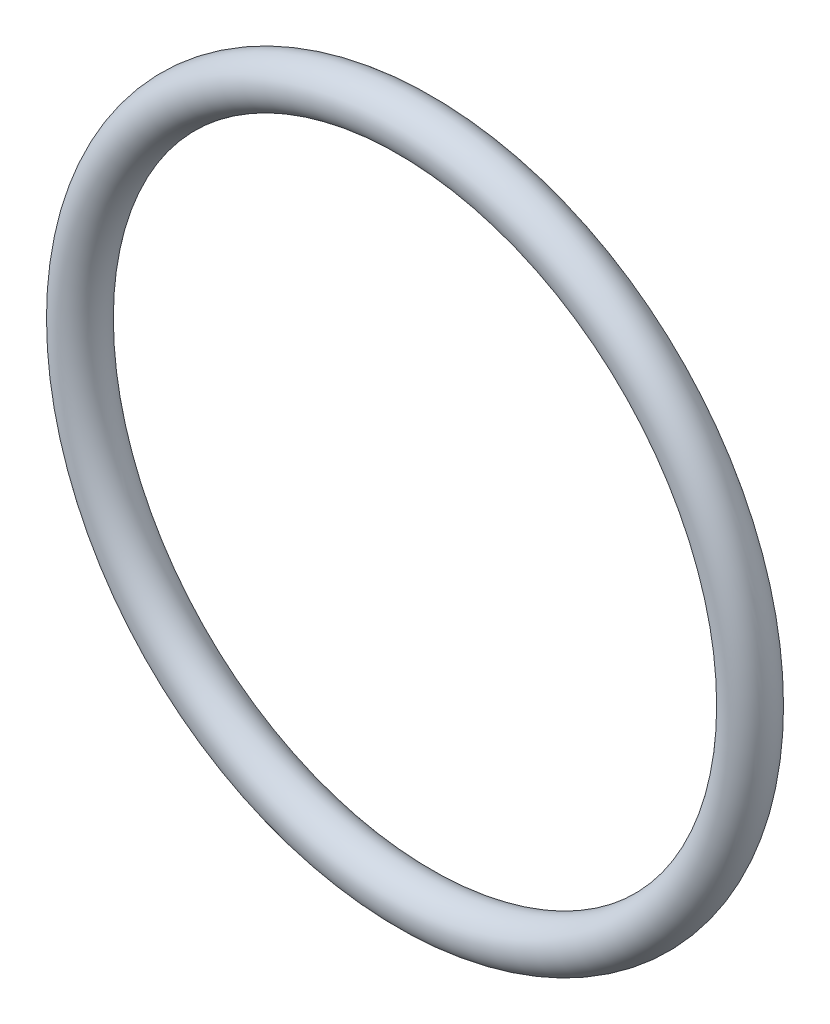
SolidWorks part; units mm, degrees
ref_plane "前视基准面" through (0, 0, 0) normal (0, 0, 1) x (1, 0, 0)
ref_plane "上视基准面" through (0, 0, 0) normal (0, 1, 0) x (1, 0, 0)
ref_plane "右视基准面" through (0, 0, 0) normal (1, 0, 0) x (0, 0, -1)
sketch "草图1" plane through (0, 0, 0) normal (0, 0, 1) x (1, 0, 0)
  circle A0 centre (0, 0) radius 8.5
  dimension "D1" = 17
sweep "扫描1" add path "草图1" circular profile diameter 1.2 parameters "D3"=1.2
ref_axis "基准轴1" through (0, 0, 0.66) along (0, 0, -1)
